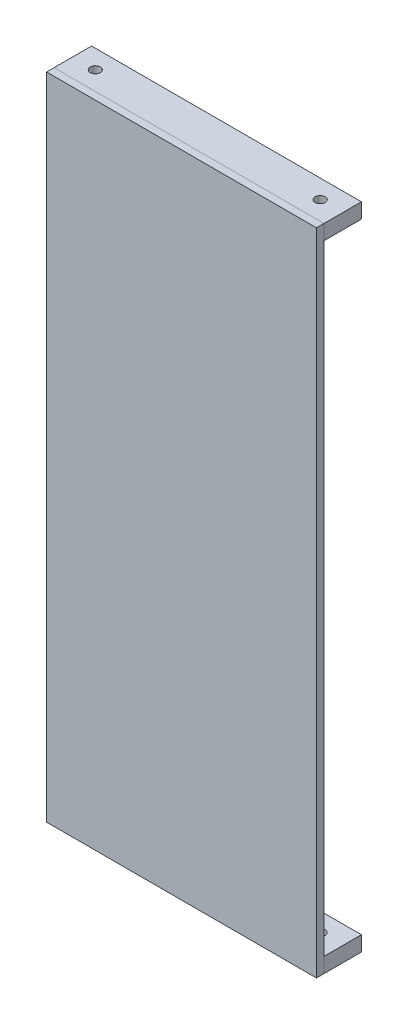
SolidWorks part; units mm, degrees
material "Pine"
ref_plane "Front Plane" through (0, 0, 0) normal (0, 0, 1) x (1, 0, 0)
ref_plane "Top Plane" through (0, 0, 0) normal (0, 1, 0) x (1, 0, 0)
ref_plane "Right Plane" through (0, 0, 0) normal (1, 0, 0) x (0, 0, -1)
sketch "Sketch1" plane through (0, 0, 0) normal (0, 0, 1) x (1, 0, 0)
  line L1 (-54, -130) -> (54, -130)
  line L2 (-54, -130) -> (-54, 130)
  line L3 (-54, 130) -> (54, 130)
  line L4 (54, -130) -> (54, 130)
  dimension "D1" = 260
  dimension "D2" = 108
  dimension "D3" = 54
  dimension "D4" = 130
extrude "Boss-Extrude1" add sketch "Sketch1" along normal blind 1.5 and the other way blind 1.5
sketch "Sketch2" plane through (0, 130, 0) normal (0, 1, 0) x (1, 0, 0)
  line L0 (-54, 1.5) -> (-54, -1.5) construction
  line L1 (54, 1.5) -> (-54, 1.5)
  line L2 (54, 1.5) -> (54, 16.5)
  line L3 (54, 16.5) -> (-54, 16.5)
  line L4 (-54, 1.5) -> (-54, 16.5)
  line L5 (54, 9) -> (-54, 9) construction
  circle A0 centre (45, 9) radius 2
  circle A1 centre (-45, 9) radius 2
  point P13 (38.4735, 7.8353)
  point P14 (0, 0)
  point P15 (-38.7749, 8.8399)
  dimension "D4" = 4
  dimension "D5" = 4
  dimension "D1" = 15
  dimension "D2" = 90
  dimension "D3" = 45
extrude "Boss-Extrude2" add sketch "Sketch2" against normal blind 6 separate body
pattern_linear "LPattern1" count 2 spacing 254 along (0, -1, 0) of "Boss-Extrude2"
